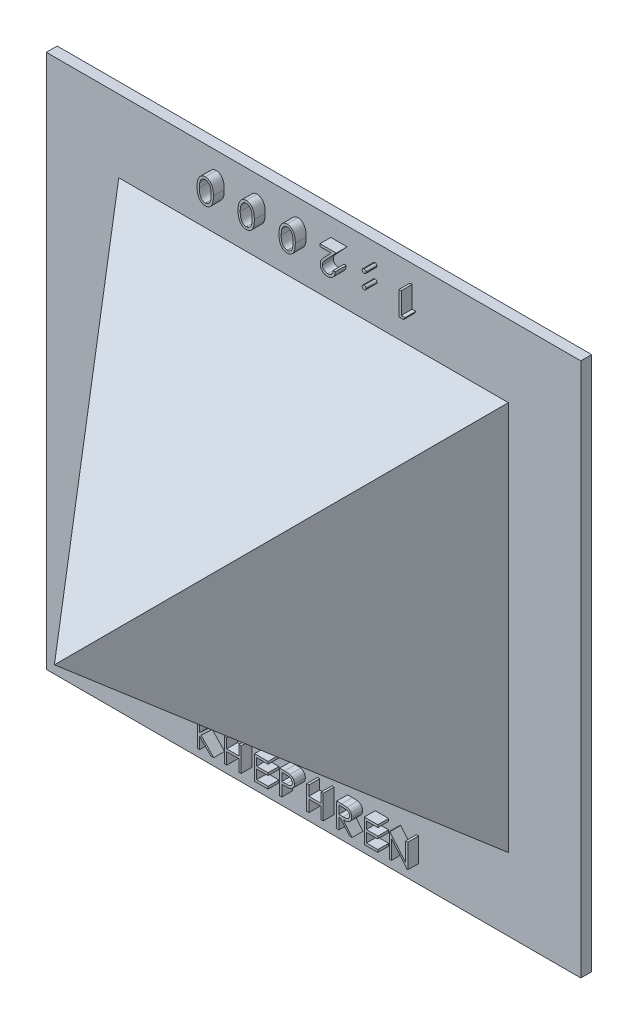
SolidWorks part; units mm, degrees
ref_plane "Plan de face" through (0, 0, 0) normal (0, 0, 1) x (1, 0, 0)
ref_plane "Plan de dessus" through (0, 0, 0) normal (0, 1, 0) x (1, 0, 0)
ref_plane "Plan de droite" through (0, 0, 0) normal (1, 0, 0) x (0, 0, -1)
sketch "Esquisse1" plane through (0, 0, 0) normal (0, 0, 1) x (1, 0, 0)
  line L1 (0, 0) -> (107.58, 0)
  line L2 (0, 0) -> (0, 107.58)
  line L3 (0, 107.58) -> (107.58, 107.58)
  line L4 (107.58, 0) -> (107.58, 107.58)
  dimension "D1" = 107.58
extrude "Boss.-Extru.1" add sketch "Esquisse1" along normal blind 95.9 draft 36.93
sketch "Esquisse3" plane through (0, 0, 0) normal (0, 0, -1) x (-1, 0, 0)
  line L8 (20, -20) -> (20, 127.58)
  line L9 (20, 127.58) -> (-127.58, 127.58)
  line L10 (-127.58, 127.58) -> (-127.58, -20)
  line L11 (-127.58, -20) -> (20, -20)
  line L12 (20, -20) -> (20, 127.58)
  line L13 (20, 127.58) -> (-127.58, 127.58)
  line L14 (-127.58, 127.58) -> (-127.58, -20)
  line L15 (-127.58, -20) -> (20, -20)
  dimension "D1" = 20
extrude "Boss.-Extru.3" add sketch "Esquisse3" along normal blind 3 separate body
sketch "Esquisse2" plane through (0, 0, -3) normal (0, 0, -1) x (-1, 0, 0)
  line L0 (0, 0) -> (-107.58, 0) construction
  line L1 (0, 107.58) -> (0, 0) construction
  circle A0 centre (-53.79, 53.79) radius 23.25
  point P5 (-53.79, 0)
  point P8 (0, 53.79)
  dimension "D1" = 46.5
extrude "Boss.-Extru.2" [suppressed] add sketch "Esquisse2" along normal blind 30
sketch "Esquisse4" plane through (0, 0, 0) normal (0, 0, 1) x (1, 0, 0)
  line L0 (23.9145, -15) -> (83.6655, -15) construction
  line L1 (24.2886, 122.58) -> (83.2914, 122.58) construction
  line L2 (0, 0) -> (107.58, 0) construction
  line L3 (127.58, -20) -> (-20, -20) construction
  line L5 (-20, 127.58) -> (127.58, 127.58) construction
  line L6 (107.58, 107.58) -> (0, 107.58) construction
  text T0 "KHEPHREN" font "Century Gothic" height in points 25
  text T1 "1:2000" font "Century Gothic" height in points 25
  point P6 (53.79, 0)
  point P7 (53.79, -15)
  point P12 (53.79, 107.58)
  point P13 (53.79, 122.58)
  dimension "D1" = 5
  dimension "D2" = 5
extrude "Boss.-Extru.4" add sketch "Esquisse4" along normal blind 3
